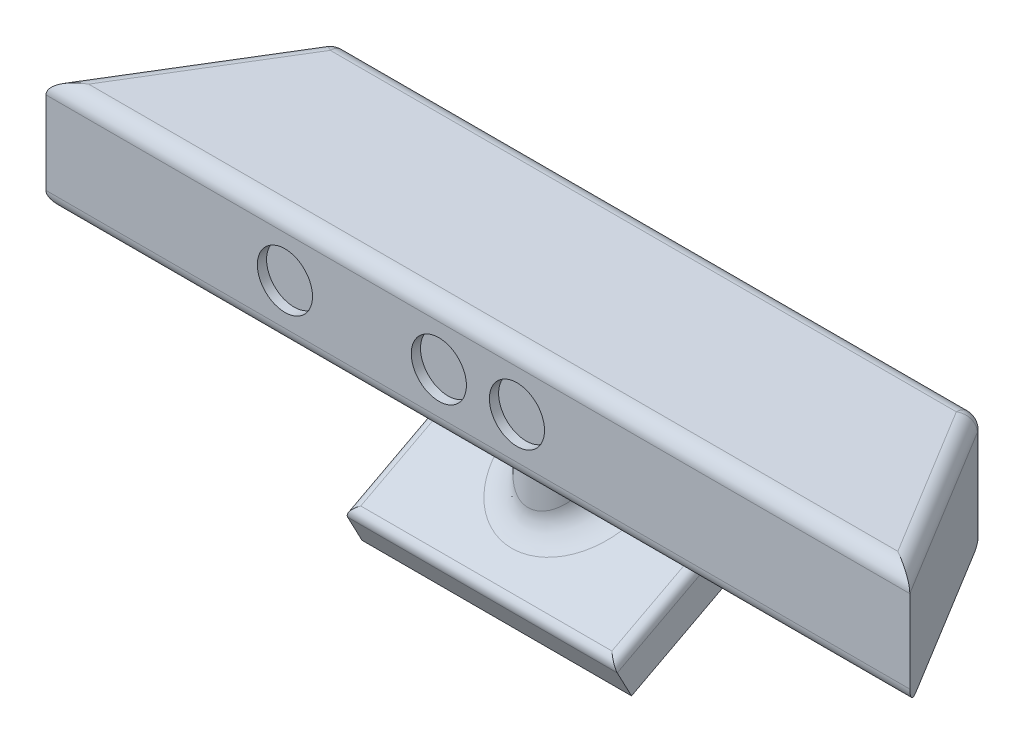
SolidWorks part; units mm, degrees
ref_plane "Front Plane" through (0, 0, 0) normal (0, 0, 1) x (1, 0, 0)
ref_plane "Top Plane" through (0, 0, 0) normal (0, 1, 0) x (1, 0, 0)
ref_plane "Right Plane" through (0, 0, 0) normal (1, 0, 0) x (0, 0, -1)
sketch "Sketch1" plane through (0, 0, 0) normal (0, 0, 1) x (1, 0, 0)
  line L1 (-141, 18.5) -> (141, 18.5)
  line L2 (-141, 18.5) -> (-141, -18.5)
  line L3 (-141, -18.5) -> (141, -18.5)
  line L4 (141, 18.5) -> (141, -18.5)
  point P4 (0, 18.5)
  point P6 (-141, 0)
  dimension "D1" = 282
  dimension "D2" = 37
extrude "Extrude1" add sketch "Sketch1" along normal blind 59
sketch "Sketch2" plane through (0, 0, 59) normal (0, 0, 1) x (1, 0, 0)
  line L0 (-141, 18.5) -> (-141, -18.5) construction
  line L1 (-12.75, 0) -> (12.75, 0) construction
  line L2 (0, 6.704) -> (0, -6.3922) construction
  circle A0 centre (-63, 0) radius 9
  circle A1 centre (-12.75, 0) radius 9
  circle A2 centre (12.75, 0) radius 9
  point P8 (0, 0)
  dimension "D1" = 78
  dimension "D2" = 18
  dimension "D3" = 18
  dimension "D4" = 18
  dimension "D5" = 12.75
  dimension "D6" = 12.75
extrude "Extrude2" cut sketch "Sketch2" against normal blind 3
sketch "Sketch6" plane through (0, 18.5, 0) normal (0, 1, 0) x (-1, 0, 0)
  line L0 (141, 0) -> (105, 0)
  line L1 (-141, 0) -> (141, 0) construction
  line L2 (105, 0) -> (141, 59)
  line L4 (141, 59) -> (141, 0)
  line L6 (-141, 59) -> (-105, 0)
  line L7 (-105, 0) -> (-141, 0)
  line L8 (-141, 0) -> (-141, 59)
  dimension "D1" = 36
extrude "Extrude5" cut sketch "Sketch6" against normal up to surface (37 mm away) up to face at (0, -18.5, 29.5)
fillet "Fillet3" radius 5 9 edges at (0, -18.5, 0) (105, 0, 0) (0, 18.5, 0) (-105, 0, 0) (-123, -18.5, 29.5) (-123, 18.5, 29.5) (0, -18.5, 59) (0, 18.5, 59) (123, 18.5, 29.5)
sketch "Sketch3" plane through (0, -18.5, 0) normal (0, -1, 0) x (1, 0, 0)
  circle A0 centre (0, 30.6373) radius 11.9694
extrude "Extrude3" add sketch "Sketch3" along normal blind 32
sketch "Sketch5" plane through (0, 0, 0) normal (1, 0, 0) x (0, 0, -1)
  line L0 (-58.9, -55.5) -> (-52.8452, -67.0039)
  line L1 (-52.8452, -67.0039) -> (11.7536, -33.0039)
  line L2 (11.7536, -33.0039) -> (5.6988, -21.5)
  line L3 (5.6988, -21.5) -> (-58.9, -55.5)
  dimension "D1" = 73
  dimension "D2" = 13
extrude "Extrude4" add sketch "Sketch5" along normal blind 44 and the other way blind 44
fillet "Fillet1" radius 10 1 edges at (0, -34.3248, 18.6679)
fillet "Fillet2" radius 3 4 edges at (-44, -38.5, 26.6006) (0, -21.5, -5.6988) (44, -38.5, 26.6006) (0, -55.5, 58.9)
split "Split1" resulting bodies 107 108 split by face at (2.9286, -18.5, 29.5)
